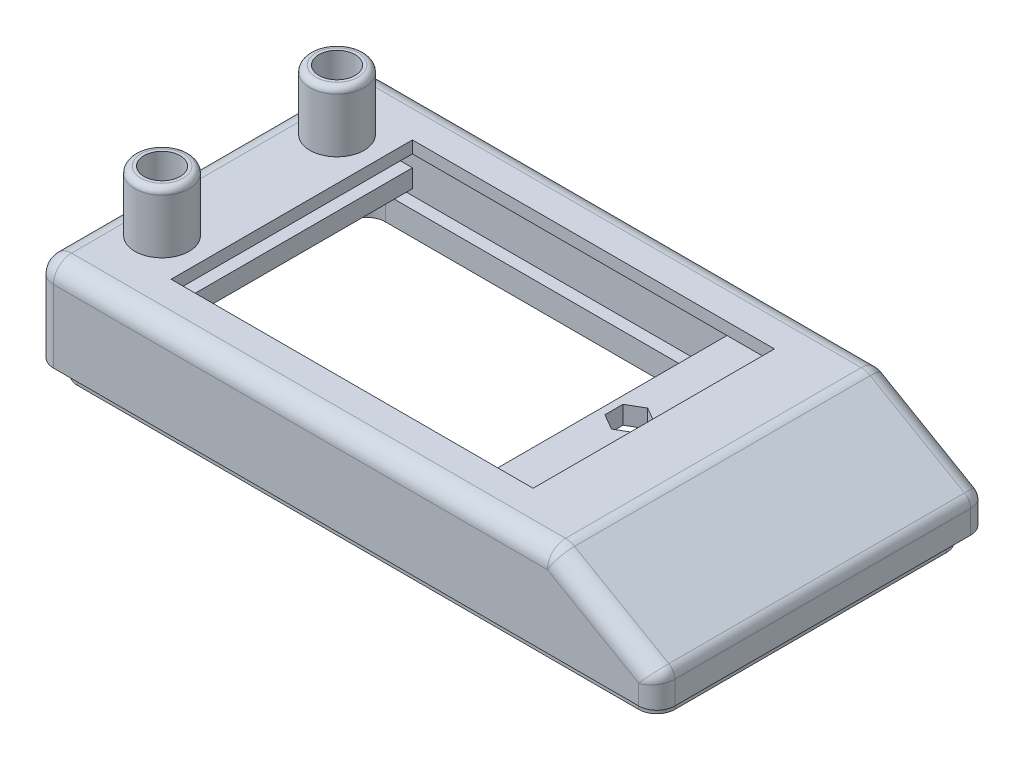
SolidWorks part; units mm, degrees
ref_plane "Ebene vorne" through (0, 0, 0) normal (0, 0, 1) x (1, 0, 0)
ref_plane "Ebene oben" through (0, 0, 0) normal (0, 1, 0) x (1, 0, 0)
ref_plane "Ebene rechts" through (0, 0, 0) normal (1, 0, 0) x (0, 0, -1)
sketch "Skizze1" plane through (0, 0, 0) normal (0, 1, 0) x (1, 0, 0)
  line L0 (0, 0) -> (103, 0)
  line L1 (-55, 0) -> (55, 0) construction
  line L2 (103, 0) -> (103, 55)
  line L3 (103, 55) -> (0, 55)
  line L4 (0, -55) -> (0, 55) construction
  line L5 (0, 55) -> (0, 0)
  dimension "D1" = 103
  dimension "D2" = 55
extrude "Aufsatz-Linear austragen1" add sketch "Skizze1" along normal blind 15
chamfer "Deckel_vorne" distance 10 angle 60 1 edges at (103, 15, -27.5) first distance on face at (103, 7.5, -27.5)
shell "Wandung1" thickness 2 removed face at (51.5, 0, -27.5)
fillet "Deckel_vorne_2" radius 2 1 edges at (103, 5, -27.5)
sketch "Skizze2" plane through (0, 15, 0) normal (0, 1, 0) x (1, 0, 0)
  line L0 (75, 7.5) -> (75, 47.5)
  line L1 (75, 47.5) -> (15, 47.5)
  line L2 (15, 47.5) -> (15, 7.5)
  line L3 (15, 7.5) -> (75, 7.5)
  line L6 (-8.25, 0) -> (8.25, 0) construction
  line L12 (0, -8.25) -> (0, 8.25) construction
  dimension "D1" = 60
  dimension "D2" = 40
  dimension "D3" = 15
  dimension "D4" = 7.5
extrude "Einsparung für Halterplatte" cut sketch "Skizze2" against normal up to surface (2 mm away) up to face at (43.5718, 13, -27.5)
ref_plane "Ebene_Magnet" through (0, 1.5, 0) normal (0, -1, 0) x (-1, 0, 0)
sketch "Skizze5" plane through (0, 1.5, 0) normal (0, -1, 0) x (-1, 0, 0)
  line L0 (-101, 53) -> (-2, 53) construction
  line L1 (-101, 2) -> (-101, 53) construction
  line L2 (-2, 2) -> (-101, 2) construction
  line L3 (-2, 53) -> (-2, 2) construction
  line L4 (-101, 53) -> (-2, 53)
  line L5 (-101, 2) -> (-101, 53)
  line L6 (-2, 2) -> (-101, 2)
  line L7 (-2, 53) -> (-2, 2)
  line L8 (-4, 51) -> (-4, 4)
  line L9 (-4, 4) -> (-99, 4)
  line L10 (-99, 4) -> (-99, 51)
  line L11 (-99, 51) -> (-4, 51)
  dimension "D1" = 2
extrude "Magnetaufsatz" add sketch "Skizze5" along normal blind 4
fillet "Verrundung4" radius 3 1 edges at (0, 7.5, -55)
fillet "Verrundung5" radius 3 1 edges at (0, 7.5, 0)
fillet "Verrundung7" radius 3 5 edges at (0.8787, 15, -54.1213) (0.8787, 15, -0.8787) (44.3397, 15, -55) (0, 15, -27.5) (44.3397, 15, 0)
fillet "Verrundung8" radius 3 9 edges at (103, 1.9226, 0) (102.7321, 4.8453, 0) (96.4378, 8.7887, 0) (87.2014, 14.1213, -0.8787) (103, 1.9226, -55) (102.7321, 4.8453, -55) (96.4378, 8.7887, -55) (87.2014, 14.1213, -54.1213) (85.6795, 15, -27.5)
sketch "Skizze6" plane through (0, 13, 0) normal (0, -1, 0) x (1, 0, 0)
  line L0 (15, -7.5) -> (10, -7.5)
  line L1 (10, -7.5) -> (10, -47.5)
  line L2 (10, -47.5) -> (15, -47.5)
  line L3 (15, -47.5) -> (15, -7.5)
  dimension "D1" = 5
extrude "Aufsatz-Linear austragen2" add sketch "Skizze6" along normal blind 5
sketch "Skizze8" plane through (15, 0, 0) normal (1, 0, 0) x (0, 0, -1)
  line L0 (7.5, 13) -> (7.5, 11)
  line L1 (7.5, 8) -> (7.5, 13) construction
  line L2 (7.5, 11) -> (47.5, 11)
  line L3 (47.5, 8) -> (47.5, 13) construction
  line L4 (47.5, 11) -> (47.5, 13)
  line L5 (47.5, 13) -> (7.5, 13)
  line L6 (47.5, 15) -> (7.5, 15) construction
  dimension "D1" = 2
  dimension "D2" = 2
extrude "Schnitt-Linear austragen1" cut sketch "Skizze8" against normal blind 3.5
sketch "Skizze13" plane through (0, 15, 0) normal (0, 1, 0) x (1, 0, 0)
  line L0 (3, 3) -> (84.8756, 3) construction
  line L4 (3, 52) -> (3, 3) construction
  line L5 (15, 27.5) -> (3, 27.5) construction
  line L6 (15, 47.5) -> (15, 7.5) construction
  circle A1 centre (8, 13) radius 4.5
  circle A2 centre (8, 42) radius 4.5
  dimension "D1" = 10
  dimension "D2" = 9
  dimension "D3" = 5
extrude "Aufsatz-Linear austragen5" add sketch "Skizze13" along normal blind 10
sketch "Skizze15" plane through (0, 25, 0) normal (0, 1, 0) x (1, 0, 0)
  circle A0 centre (8, 13) radius 3
  circle A1 centre (8, 42) radius 3
  dimension "D1" = 6
  dimension "D2" = 6
extrude "Schnitt-Linear austragen5" cut sketch "Skizze15" against normal up to surface (17 mm away) up to face at (12.5, 8, -27.5)
fillet "Verrundung11" radius 1 2 edges at (8, 25, -8.5) (8, 25, -46.5)
fillet "Verrundung12" radius 3 4 edges at (101, -1.25, -2) (101, -1.25, -53) (2, -1.25, -2) (2, -1.25, -53)
fillet "Verrundung13" radius 3 4 edges at (4, -0.5, -4) (4, -0.5, -51) (99, -0.5, -4) (99, -0.5, -51)
sketch "Skizze21" plane through (0, 0, -53) normal (0, 0, 1) x (1, 0, 0)
  line L1 (67.1436, 10) -> (67.1436, 13)
  line L2 (85.1436, 13) -> (2, 13) construction
  line L3 (67.1436, 13) -> (85.1436, 13)
  line L4 (85.1436, 13) -> (101, 3.8453)
  line L6 (67.1436, 10) -> (75.7109, 10)
  line L7 (75.7109, 10) -> (101, 3.8453)
  dimension "D1" = 3
  dimension "D2" = 18
extrude "Aufsatz-Linear austragen9" add sketch "Skizze21" along normal up to surface (51 mm away) up to face at (58.2287, 6.5691, -2)
sketch "Skizze22" plane through (0, 13, 0) normal (0, 1, 0) x (1, 0, 0)
  line L0 (3, 27.5) -> (84.8756, 27.5) construction
  line L1 (3, 52) -> (3, 3) construction
  line L2 (84.8756, 3) -> (84.8756, 52) construction
  line L4 (73.5937, 29) -> (70.9956, 30.5)
  line L5 (70.9956, 30.5) -> (68.3976, 29)
  line L6 (68.3976, 29) -> (68.3976, 26)
  line L7 (68.3976, 26) -> (70.9956, 24.5)
  line L8 (70.9956, 24.5) -> (73.5937, 26)
  line L9 (73.5937, 26) -> (73.5937, 29)
  circle A0 centre (70.9956, 27.5) radius 2.5981 construction
  dimension "D1" = 3
  dimension "D2" = 13.88
  dimension "D3" = 1.5
extrude "Schnitt-Linear austragen6" cut sketch "Skizze22" against normal through all
